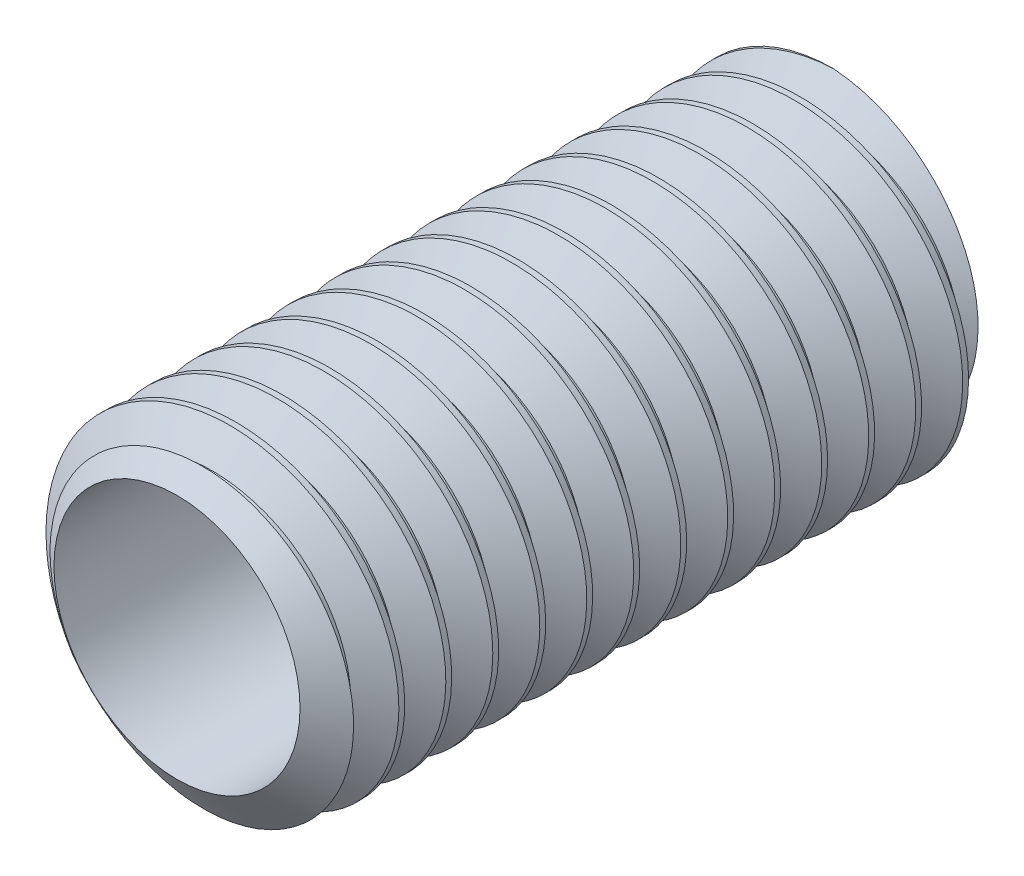
SolidWorks part; units mm, degrees
other "DetailItem1"
ref_plane "Front Plane" through (0, 0, 0) normal (0, 0, 1) x (1, 0, 0)
ref_plane "Top Plane" through (0, 0, 0) normal (0, 1, 0) x (1, 0, 0)
ref_plane "Right Plane" through (0, 0, 0) normal (1, 0, 0) x (0, 0, -1)
sketch "Sketch1" plane through (0, 0, 0) normal (0, 0, 1) x (1, 0, 0)
  circle A0 centre (0, 0) radius 3.175
  dimension "OD" = 6.35
extrude "Extrude1" add sketch "Sketch1" against normal blind 12.7
sketch "Sketch2" plane through (0, 0, 0) normal (0, 0, 1) x (1, 0, 0)
  circle A0 centre (0, 0) radius 3.175 construction
  circle A1 centre (0, 0) radius 3.175
curve "Helix/Spiral1" pitch 0.9071 height 13.6071 turns 15 parameters "pitch"=0.9071
sketch "Sketch3" plane through (0, 0, 0) normal (1, 0, 0) x (0, 0, -1)
  line L0 (-0.7937, 3.175) -> (-0.4536, 2.5858)
  line L1 (-0.4536, 2.5858) -> (-0.3402, 2.5858)
  line L2 (-0.3402, 2.5858) -> (0, 3.175)
  line L3 (-0.7937, 3.175) -> (0, 3.175)
  line L4 (-0.3969, 3.175) -> (-0.3969, 2.5858) construction
  line L5 (-0.6237, 2.8804) -> (-0.1701, 2.8804) construction
  line L6 (0, 3.175) -> (0, -3.175) construction
  dimension "D1" = 0.1134
  dimension "D2" = 0.4536
  dimension "D3" = 60
sweep "Cut-Sweep1 1/4-28 threads" cut profiles "Sketch3" path "Helix/Spiral1"
sketch "Sketch4" plane through (0, 0, 0) normal (1, 0, 0) x (0, 0, -1)
  line L0 (0.5904, 3.175) -> (0, 2.3318)
  line L1 (0, 2.3318) -> (0, 3.175)
  line L2 (0.5904, 3.175) -> (0, 3.175)
  line L3 (-0.7937, 3.175) -> (0, 3.175) construction
  line L4 (0, 0) -> (7.0209, 0) construction
  dimension "D1" = 55
  dimension "D2" = 0.254
revolve "Cut-Revolve1" cut sketch "Sketch4" angle 360 about L4
sketch "Sketch11" plane through (0, 0, -12.7) normal (0, 0, -1) x (-1, 0, 0)
  circle A0 centre (0, 0) radius 2.375
  dimension "D1" = 4.75
extrude "Cut-Extrude3" cut sketch "Sketch11" against normal through all
sketch "Sketch6" plane through (0, 0, -12.7) normal (0, 0, -1) x (-1, 0, 0)
  circle A0 centre (0, 0) radius 4.7625
  dimension "head dia" = 9.525
extrude "Extrude2" [suppressed] add sketch "Sketch6" along normal blind 6.35
sketch "Sketch7" [suppressed] plane through (0, 0, -19.05) normal (0, 0, -1) x (-1, 0, 0)
  line L1 (0, 2.7496) -> (-2.3813, 1.3748)
  line L2 (-2.3813, 1.3748) -> (-2.3813, -1.3748)
  line L3 (-2.3813, -1.3748) -> (0, -2.7496)
  line L4 (0, -2.7496) -> (2.3813, -1.3748)
  line L5 (2.3813, -1.3748) -> (2.3813, 1.3748)
  line L6 (2.3813, 1.3748) -> (0, 2.7496)
  circle A0 centre (0, 0) radius 2.3813 construction
  dimension "hex dia" = 4.7625
extrude "Cut-Extrude1" [suppressed] cut sketch "Sketch7" against normal blind 3.5719
sketch "Sketch8" [suppressed] plane through (0, 0, -19.05) normal (0, 0, -1) x (-1, 0, 0)
  circle A0 centre (0, 0) radius 2.7496
extrude "Cut-Extrude2" [suppressed] cut sketch "Sketch8" against normal through all draft 45
chamfer "Chamfer1" [suppressed] distance 0.4763 angle 45
sketch "Sketch10" [suppressed] plane through (0, 0, -12.7) normal (0, 0, 1) x (1, 0, 0)
  circle A1 centre (0, 0) radius 3.175
  circle A2 centre (0, 0) radius 3.175
  dimension "D1" = 0
ref_plane "Plane1" through (0, 0, -31.75) normal (0, 0, 1) x (1, 0, 0)
extrude "partial thread" [suppressed] add sketch "Sketch10" along normal up to surface (12.7 mm away) separate body
chamfer "Chamfer2" [suppressed] distance 0.127 angle 45
combine bodies "Combine1" [suppressed] operation type add bodies to combine 107 108
sketch "Sketch9" plane through (0, 0, 0) normal (1, 0, 0) x (0, 0, -1)
  line L0 (0, 3.175) -> (0, -3.175) construction
  line L1 (2.2679, 3.175) -> (2.2679, -3.175) construction
  dimension "D1" = 2.2679
equation "\"D3@Helix/Spiral1\" = \"screw length@Extrude1\"+\"pitch@Helix/Spiral1\""
equation "\"D1@Sketch3\" = \"pitch@Helix/Spiral1\"*.125"
equation "\"D2@Sketch3\" = \"pitch@Helix/Spiral1\"*.5"
equation "\"D1@Cut-Extrude1\" = \"hex dia@Sketch7\"*.75"
equation "\"D1@Chamfer1\" = \"head dia@Sketch6\"*.05"
equation "\"D1@Sketch9\" = \"pitch@Helix/Spiral1\"*2.5"
equation "\"D1@Chamfer2\"=\"OD@Sketch1\"*.02"
